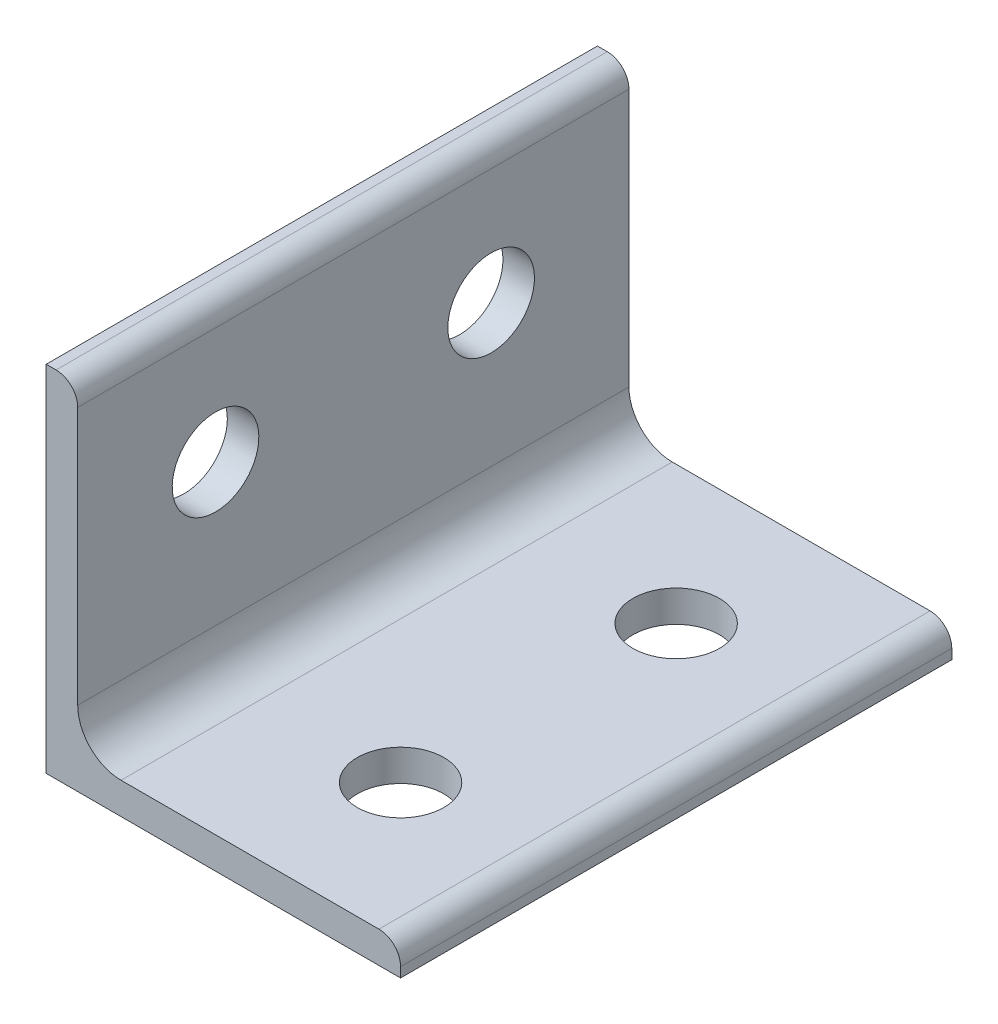
SolidWorks part; units mm, degrees
note: '?' marks a value the reader was unsure of.
other "Connection Feature"
ref_plane "Front Plane" through (0, 0, 0) normal (0, 0, 1) x (1, 0, 0)
ref_plane "Top Plane" through (0, 0, 0) normal (0, 1, 0) x (1, 0, 0)
ref_plane "Right Plane" through (0, 0, 0) normal (1, 0, 0) x (0, 0, -1)
ref_axis "Axis1" through (0, 0, 55) along (0, 0, -1)?
sketch "Sketch1" plane through (0, 0, 0) normal (0, 0, 1) x (1, 0, 0)
  line L0 (0, 90) -> (0, 0)
  line L1 (0, 0) -> (90, 0) construction
  line L2 (0, 0) -> (0, 90) construction
  line L3 (0, 90) -> (90, 90) construction
  line L4 (90, 0) -> (90, 90) construction
  line L5 (0, 0) -> (90, 90) construction
  line L6 (0, 90) -> (90, 0) construction
  line L7 (0, 0) -> (90, 0)
  line L8 (90, 0) -> (90, 2.5)
  line L9 (84.5, 8) -> (19, 8)
  line L10 (8, 19) -> (8, 84.5)
  line L11 (2.5, 90) -> (0, 90)
  line L12 (0, -55) -> (0, 55) construction
  line L13 (55, 0) -> (-55, 0) construction
  arc A0 (19, 8) -> (8, 19) centre (19, 19) cw
  arc A1 (90, 2.5) -> (84.5, 8) centre (84.5, 2.5) ccw
  arc A2 (8, 84.5) -> (2.5, 90) centre (2.5, 84.5) ccw
  point P0 (0, 0)
  point P13 (90, 8)
  point P16 (8, 90)
  dimension "D1" = 11
  dimension "D2" = 5.5
  dimension "h" = 90
  dimension "b" = 90
  dimension "t" = 8
extrude "Boss-Extrude1" add sketch "Sketch1" along normal mid plane 140
sketch "Sketch4" plane through (0, 8, 0) normal (0, 1, 0) x (1, 0, 0)
  line L0 (0, -70) -> (0, 70) construction
  line L1 (84.5, -70) -> (19, -70) construction
  point P0 (55, -35)
  dimension "D1" = 55
  dimension "D2" = 35
hole_wizard "Ø22.0 (22) Diameter Hole1" positions "Sketch4" profile "Sketch3" hole size "Ø22.0" standard "ISO" end condition through all
sketch "Sketch3" plane through (55, 8, 35) normal (1, 0, 0) x (0, 0, 1)
  line L0 (0, 0) -> (0, 8)
  line L1 (0, 8) -> (11, 8)
  line L2 (11, 8) -> (11, 0)
  line L5 (11, 0) -> (0, 0)
  line L11 (0, -6.35) -> (0, 107.95) construction
  dimension "Thru Hole Dia." = 22
  dimension "Thru Hole Depth" = 8
pattern_linear "LPattern1" count 2 spacing 70 along (0, 0, -1) of "Ø22.0 (22) Diameter Hole1"
pattern_circular "CirPattern1" count 2 every 90 about axis through (0, 0, 55) along (0, 0, -1) of "Ø22.0 (22) Diameter Hole1", "LPattern1"
